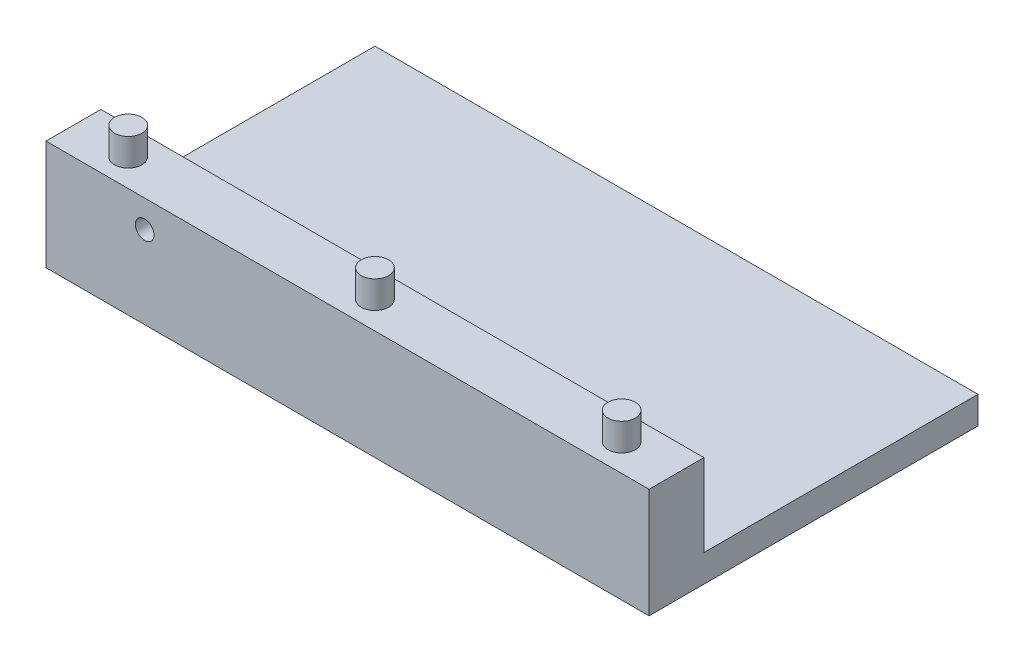
SolidWorks part; units mm, degrees
ref_plane "Front Plane" through (0, 0, 0) normal (0, 0, 1) x (1, 0, 0)
ref_plane "Top Plane" through (0, 0, 0) normal (0, 1, 0) x (1, 0, 0)
ref_plane "Right Plane" through (0, 0, 0) normal (1, 0, 0) x (0, 0, -1)
sketch "Sketch1" plane through (0, 0, 0) normal (0, 1, 0) x (1, 0, 0)
  line L0 (-69.85, -38.1) -> (69.85, -38.1)
  line L1 (-69.85, -38.1) -> (-69.85, 38.1)
  line L2 (69.85, -38.1) -> (69.85, 38.1)
  line L3 (-69.85, 38.1) -> (69.85, 38.1)
  line L4 (-69.85, -38.1) -> (69.85, 38.1) construction
  line L5 (69.85, -38.1) -> (-69.85, 38.1) construction
  point P1 (0, 0)
  dimension "D1" = 76.2
  dimension "D2" = 139.7
extrude "Boss-Extrude1" add sketch "Sketch1" along normal blind 6.35
sketch "Sketch2" plane through (0, 6.35, 0) normal (0, 1, 0) x (1, 0, 0)
  line L0 (-69.85, 38.1) -> (-69.85, -38.1) construction
  line L1 (-69.85, -38.1) -> (69.85, -38.1)
  line L2 (69.85, -38.1) -> (69.85, -25.4)
  line L3 (69.85, -38.1) -> (69.85, 38.1) construction
  line L4 (69.85, -25.4) -> (-69.85, -25.4)
  line L5 (-69.85, -25.4) -> (-69.85, -38.1)
  dimension "D2" = 12.7
extrude "Boss-Extrude2" add sketch "Sketch2" along normal blind 19.05
sketch "Sketch3" plane through (0, 6.35, 0) normal (0, 1, 0) x (1, 0, 0)
  line L1 (-69.85, -38.1) -> (69.85, -38.1) construction
  line L2 (-69.85, 38.1) -> (-69.85, -25.4) construction
  circle A0 centre (-53.34, -21.59) radius 2.032
  dimension "D1" = 4.064
  dimension "D2" = 16.51
  dimension "D3" = 16.51
extrude "Cut-Extrude1" cut sketch "Sketch3" against normal through all
sketch "Sketch4" plane through (0, 0, 0) normal (0, -1, 0) x (1, 0, 0)
  line L0 (-69.85, 38.1) -> (69.85, 38.1) construction
  line L1 (-50.927, 25.7694) -> (-55.753, 25.7694)
  line L2 (-55.753, 25.7694) -> (-58.166, 21.59)
  line L3 (-58.166, 21.59) -> (-55.753, 17.4106)
  line L4 (-55.753, 17.4106) -> (-50.927, 17.4106)
  line L5 (-50.927, 17.4106) -> (-48.514, 21.59)
  line L6 (-48.514, 21.59) -> (-50.927, 25.7694)
  circle A0 centre (-53.34, 21.59) radius 4.1794 construction
  dimension "D1" = 4.826
extrude "Cut-Extrude2" cut sketch "Sketch4" against normal blind 3.048
sketch "Sketch5" plane through (0, 25.4, 0) normal (0, 1, 0) x (1, 0, 0)
  line L0 (-69.85, -25.4) -> (-69.85, -38.1) construction
  line L3 (69.85, -25.4) -> (-69.85, -25.4) construction
  circle A0 centre (-57.15, -31.75) radius 3.175
  circle A1 centre (0, -31.75) radius 3.175
  circle A2 centre (57.15, -31.75) radius 3.175
  point P5 (-69.85, -31.75)
  dimension "D2" = 6.35
  dimension "D1" = 12.7
  dimension "D4" = 57.15
  dimension "D5" = 6.35
  dimension "D3" = 3
extrude "Boss-Extrude3" add sketch "Sketch5" along normal blind 6.35
sketch "Sketch6" plane through (0, 0, 25.4) normal (0, 0, -1) x (-1, 0, 0)
  line L0 (-69.85, 25.4) -> (69.85, 25.4) construction
  line L1 (69.85, 25.4) -> (69.85, 6.35) construction
  circle A0 centre (46.99, 19.05) radius 2.159
  dimension "D1" = 4.318
  dimension "D2" = 6.35
  dimension "D3" = 22.86
extrude "Cut-Extrude3" cut sketch "Sketch6" against normal blind 12.7
